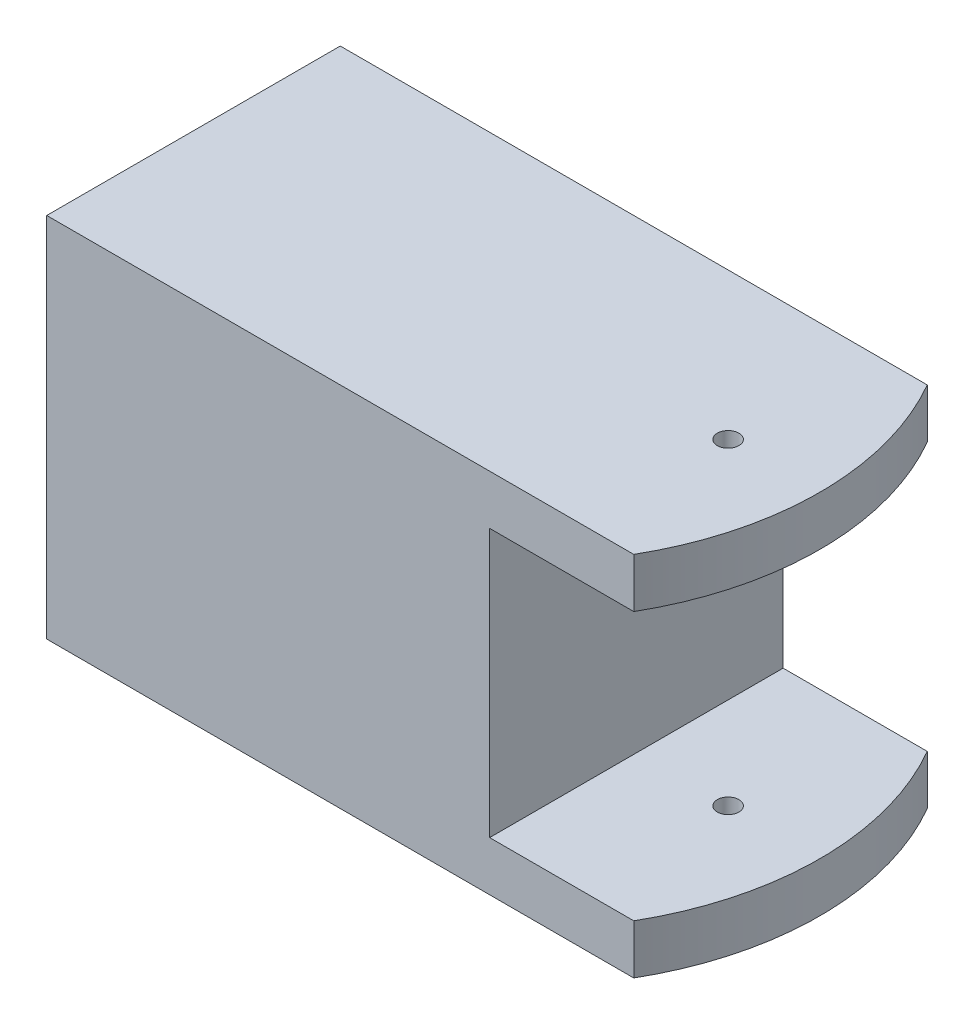
SolidWorks part; units mm, degrees
ref_plane "Front Plane" through (0, 0, 0) normal (0, 0, 1) x (1, 0, 0)
ref_plane "Top Plane" through (0, 0, 0) normal (0, 1, 0) x (1, 0, 0)
ref_plane "Right Plane" through (0, 0, 0) normal (1, 0, 0) x (0, 0, -1)
sketch "Sketch1" plane through (0, 0, 0) normal (0, 1, 0) x (1, 0, 0)
  line L0 (0, -20) -> (0, 20) construction
  line L1 (0, -20) -> (-80, -20)
  line L3 (0, 20) -> (-80, 20)
  line L4 (-80, -20) -> (-80, 20)
  arc A1 (0, 20) -> (0, -20) centre (-34.641, 0) cw
  point P6 (0, 0)
  dimension "D3" = 40
  dimension "D1" = 40
  dimension "D2" = 80
extrude "Boss-Extrude1" add sketch "Sketch1" along normal blind 25 and the other way blind 25
sketch "Sketch3" plane through (0, 0, 0) normal (0, 0, 1) x (1, 0, 0)
  line L0 (5.359, -25) -> (5.359, 25) construction
  line L1 (-19.641, 18.25) -> (7.9634, 18.25)
  line L2 (-19.641, 18.25) -> (-19.641, -18.25)
  line L3 (-19.641, -18.25) -> (7.9634, -18.25)
  line L4 (7.9634, 18.25) -> (7.9634, -18.25)
  line L5 (-34.641, 53.7865) -> (-34.641, -45.3958) construction
  line L6 (5.359, -25) -> (5.359, 25) construction
  point P6 (7.9634, 0)
  dimension "D1" = 36.5
  dimension "D2" = 25
  dimension "D3" = 40
extrude "Cut-Extrude2" cut sketch "Sketch3" against normal through all and the other way through all
sketch "Sketch4" plane through (0, 0, 0) normal (0, 1, 0) x (1, 0, 0)
  circle A0 centre (-7.141, 0) radius 1.475
  arc A1 (0, -20) -> (0, 20) centre (-34.641, 0) ccw construction
  dimension "D1" = 27.5
extrude "Cut-Extrude3" cut sketch "Sketch4" against normal through all and the other way through all
